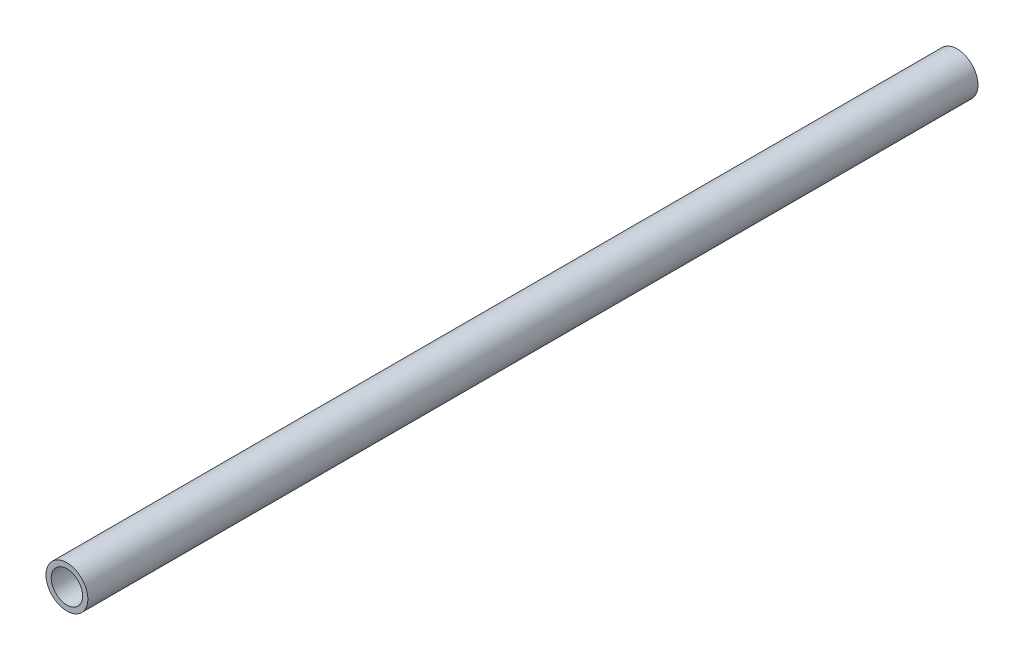
SolidWorks part; units mm, degrees
material "PC High Viscosity"
ref_plane "Front Plane" through (0, 0, 0) normal (0, 0, 1) x (1, 0, 0)
ref_plane "Top Plane" through (0, 0, 0) normal (0, 1, 0) x (1, 0, 0)
ref_plane "Right Plane" through (0, 0, 0) normal (1, 0, 0) x (0, 0, -1)
sketch "Sketch2" plane through (0, 0, 0) normal (0, 0, 1) x (1, 0, 0)
  circle A0 centre (0, 0) radius 9.525
  circle A1 centre (0, 0) radius 12.7
  dimension "D1" = 25.4
  dimension "D2" = 19.05
extrude "Boss-Extrude1" add sketch "Sketch2" along normal mid plane 539.7881
